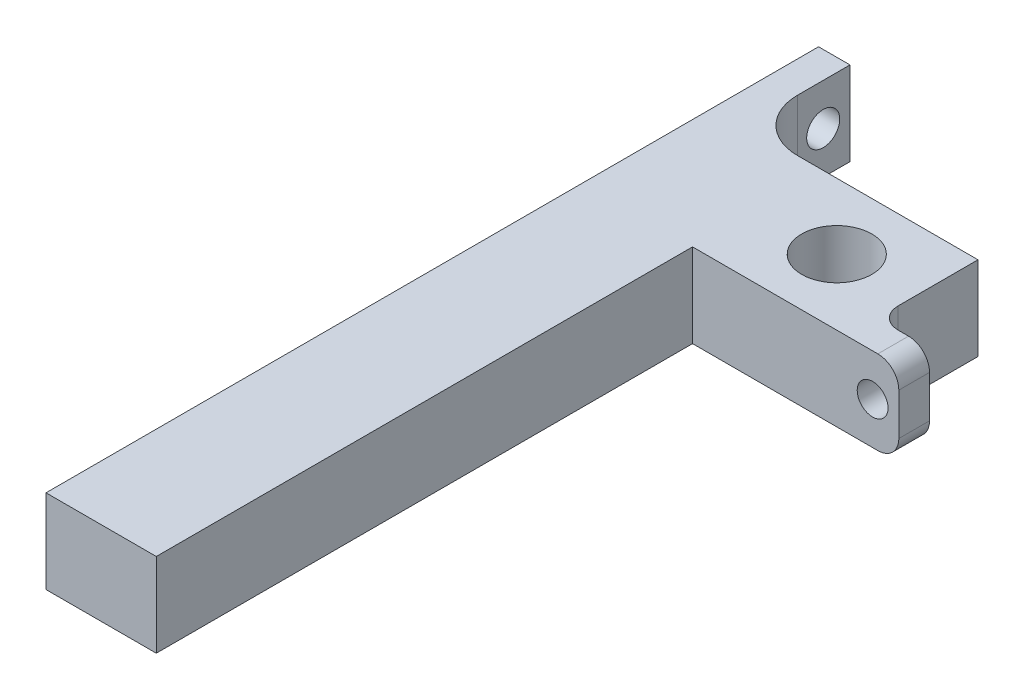
SolidWorks part; units mm, degrees
ref_plane "Front" through (0, 0, 0) normal (0, 0, 1) x (1, 0, 0)
ref_plane "Top" through (0, 0, 0) normal (0, 1, 0) x (1, 0, 0)
ref_plane "Right" through (0, 0, 0) normal (1, 0, 0) x (0, 0, -1)
sketch "Sketch1" plane through (0, 0, 0) normal (0, 1, 0) x (1, 0, 0)
  line L1 (-8.3469, 33.3364) -> (-23.0379, 33.3364)
  line L2 (-8.3469, 33.3364) -> (-8.3469, 45.8951)
  line L3 (-8.3469, 45.8951) -> (-23.0379, 45.8951)
  line L4 (-23.0379, 33.3364) -> (-23.0379, 45.8951)
  line L5 (-23.0379, 45.8951) -> (-25.5668, 45.8951)
  line L6 (-23.0379, 45.8951) -> (-23.0379, -17.8545)
  line L7 (-23.0379, -17.8545) -> (-33.5668, -17.8545)
  line L8 (-33.5668, 45.8951) -> (-33.5668, -17.8545)
  line L9 (-8.3469, 33.3364) -> (-3.3469, 33.3364)
  line L10 (-8.3469, 33.3364) -> (-8.3469, 36.2667)
  line L11 (-8.3469, 36.2667) -> (-3.3469, 36.2667)
  line L12 (-3.3469, 33.3364) -> (-3.3469, 36.2667)
  line L13 (-33.5668, 45.8951) -> (-30.5668, 45.8951)
  line L14 (-33.5668, 45.8951) -> (-33.5668, 55.8951)
  line L15 (-33.5668, 55.8951) -> (-30.5668, 55.8951)
  line L16 (-30.5668, 50.8951) -> (-30.5668, 55.8951)
  circle A0 centre (-15.5493, 39.6158) radius 3.349
  arc A1 (-30.5668, 50.8951) -> (-25.5668, 45.8951) centre (-25.5668, 50.8951) ccw
  dimension "D3" = 5
  dimension "D1" = 5
  dimension "D2" = 3
extrude "Boss-Extrude1" add sketch "Sketch1" along normal blind 8 contours L5 L8 L7 L6 L4 | L4 L1 L2 L3 A0 | L9 L12 L11 L10 region at (-15.6924, 0, -33.5296) region at (-28.4709, 0, -15.8364)
sketch "Sketch2" plane through (0, 0, -36.2667) normal (0, 0, -1) x (-1, 0, 0)
  line L0 (8.3469, 0) -> (3.3469, 0) construction
  line L1 (3.3469, 8) -> (3.3469, 0) construction
  circle A0 centre (5.8469, 4) radius 1.4722
  point P4 (5.8469, 0)
  point P7 (3.3469, 4)
extrude "Cut-Extrude1" cut sketch "Sketch2" against normal blind 10 contours A0
fillet "Fillet1" radius 2 3 edges at (-8.3469, 4, -36.2667) (-3.3469, 0, -34.8016) (-3.3469, 8, -34.8016)
sketch "Sketch3" plane through (-30.5668, 0, 0) normal (1, 0, 0) x (0, 0, -1)
  circle A0 centre (53.3374, 4.0156) radius 1.578
extrude "Cut-Extrude2" cut sketch "Sketch3" against normal blind 10 contours A0
